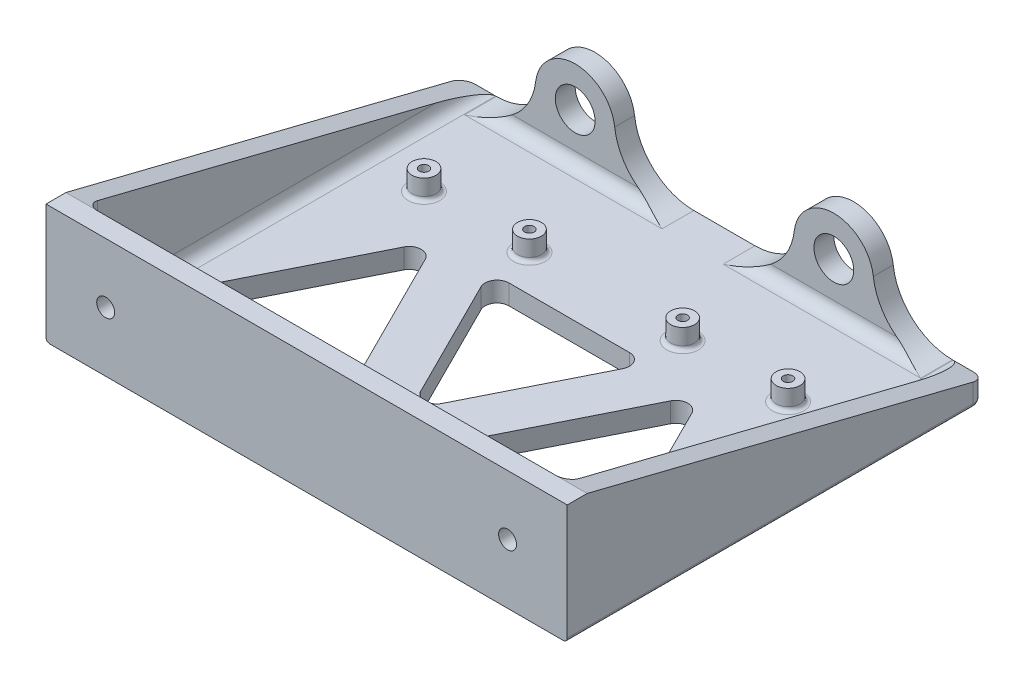
SolidWorks part; units mm, degrees
material "PMMA"
ref_plane "Front Plane" through (0, 0, 0) normal (0, 0, 1) x (1, 0, 0)
ref_plane "Top Plane" through (0, 0, 0) normal (0, 1, 0) x (1, 0, 0)
ref_plane "Right Plane" through (0, 0, 0) normal (1, 0, 0) x (0, 0, -1)
sketch "Sketch1" plane through (0, 0, 0) normal (0, 1, 0) x (1, 0, 0)
  line L7 (-45.75, -29.25) -> (-19.25, -29.25) construction
  line L8 (-45.75, -29.25) -> (-45.75, 29.25) construction
  line L9 (-45.75, 29.25) -> (-19.25, 29.25) construction
  line L10 (-19.25, -29.25) -> (-19.25, 29.25) construction
  line L11 (-45.75, -29.25) -> (-19.25, 29.25) construction
  line L12 (-45.75, 29.25) -> (-19.25, -29.25) construction
  line L13 (19.25, -29.25) -> (45.75, -29.25) construction
  line L14 (19.25, -29.25) -> (19.25, 29.25) construction
  line L15 (19.25, 29.25) -> (45.75, 29.25) construction
  line L16 (45.75, -29.25) -> (45.75, 29.25) construction
  line L17 (19.25, -29.25) -> (45.75, 29.25) construction
  line L18 (19.25, 29.25) -> (45.75, -29.25) construction
  circle A0 centre (-45.75, 29.25) radius 3
  circle A1 centre (-19.25, 29.25) radius 3
  circle A2 centre (-45.75, -29.25) radius 3
  circle A3 centre (-19.25, -29.25) radius 3
  circle A4 centre (19.25, 29.25) radius 3
  circle A5 centre (45.75, 29.25) radius 3
  circle A6 centre (45.75, -29.25) radius 3
  circle A7 centre (-45.75, 29.25) radius 1.2
  circle A8 centre (-19.25, 29.25) radius 1.2
  circle A9 centre (19.25, 29.25) radius 1.2
  circle A10 centre (-45.75, -29.25) radius 1.2
  circle A11 centre (-19.25, -29.25) radius 1.2
  circle A12 centre (45.75, -29.25) radius 1.2
  circle A13 centre (19.25, -29.25) radius 3
  circle A14 centre (19.25, -29.25) radius 1.2
  circle A15 centre (45.75, 29.25) radius 1.2
  point P0 (0, 0)
  point P6 (-32.5, 0)
  point P11 (32.5, 0)
  dimension "D5" = 6
  dimension "D6" = 2.4
  dimension "D1" = 26.5
  dimension "D2" = 58.5
  dimension "D3" = 65
  dimension "D4" = 19.25
extrude "Boss-Extrude1" add sketch "Sketch1" along normal blind 10
sketch "Sketch2" plane through (0, 0, 0) normal (0, 1, 0) x (1, 0, 0)
  line L1 (65.5, 59) -> (-65.5, 59)
  line L2 (65.5, 59) -> (65.5, -41)
  line L3 (65.5, -41) -> (-65.5, -41)
  line L4 (-65.5, 59) -> (-65.5, -41)
  line L5 (65.5, 59) -> (-65.5, -41) construction
  line L6 (65.5, -41) -> (-65.5, 59) construction
  circle A0 centre (45.75, -29.25) radius 1.2
  circle A1 centre (19.25, -29.25) radius 1.2
  circle A2 centre (-19.25, -29.25) radius 1.2
  circle A3 centre (-45.75, -29.25) radius 1.2
  circle A4 centre (-45.75, 29.25) radius 1.2
  circle A5 centre (-19.25, 29.25) radius 1.2
  circle A6 centre (19.25, 29.25) radius 1.2
  circle A7 centre (45.75, 29.25) radius 1.2
  point P0 (0, 9)
  point P33 (0, 9)
  dimension "D3" = 2.4
  dimension "D1" = 100
  dimension "D2" = 65.5
  dimension "D4" = 9
extrude "Boss-Extrude2" add sketch "Sketch2" along normal blind 5
sketch "Sketch5" plane through (0, 0, 41) normal (0, 0, 1) x (1, 0, 0)
  line L0 (65.5, 5) -> (65.5, 0) construction
  line L1 (-65.5, 0) -> (65.5, 0)
  line L2 (-65.5, 0) -> (-65.5, 30)
  line L3 (-65.5, 30) -> (65.5, 30)
  line L4 (65.5, 0) -> (65.5, 30)
  dimension "D1" = 30
extrude "Boss-Extrude4" add sketch "Sketch5" along normal blind 5
sketch "Sketch6" plane through (-65.5, 0, 0) normal (-1, 0, 0) x (0, 0, 1)
  line L0 (-59, 5) -> (41, 30)
  line L1 (41, 30) -> (41, 5)
  line L2 (41, 5) -> (-59, 5)
extrude "Boss-Extrude5" add sketch "Sketch6" against normal blind 5
mirror "Mirror1" about plane through (0, 0, 0) normal (1, 0, 0) of "Boss-Extrude5"
fillet "Fillet2" radius 3 7 edges at (-60.5, 5, -9) (-60.5, 17.5, 41) (0, 5, 41) (60.5, 17.5, 41) (60.5, 5, -9) (65.5, 2.5, -59) (-65.5, 2.5, -59)
sketch "Sketch7" plane through (0, 0, 46) normal (0, 0, 1) x (1, 0, 0)
  line L0 (-65.5, 30) -> (-65.5, 0) construction
  line L1 (65.5, 0) -> (65.5, 30) construction
  circle A0 centre (-50.5, 15) radius 2.25
  circle A1 centre (50.5, 15) radius 2.25
  point P8 (-65.5, 15)
  dimension "D1" = 4.5
  dimension "D2" = 15
  dimension "D3" = 15
extrude "Cut-Extrude2" cut sketch "Sketch7" against normal blind 5
sketch "Sketch8" plane through (0, 0, -59) normal (0, 0, -1) x (-1, 0, 0)
  line L1 (-57.5, 5) -> (57.5, 5) construction
  line L2 (-42.5, 17) -> (-42.5, 0)
  line L3 (-62.5, 0) -> (62.5, 0) construction
  line L4 (-42.5, 0) -> (-22.5, 0)
  line L5 (-22.5, 0) -> (-22.5, 17)
  circle A0 centre (-32.5, 17) radius 5
  arc A2 (-42.5, 17) -> (-22.5, 17) centre (-32.5, 17) cw
  dimension "D1" = 10
  dimension "D2" = 12
  dimension "D4" = 10
  dimension "D3" = 32.5
extrude "Boss-Extrude6" add sketch "Sketch8" against normal blind 5
fillet "Fillet5" radius 15 2 edges at (22.5, 5, -56.5) (42.5, 5, -56.5)
fillet "Fillet6" radius 3 1 edges at (32.5, 5, -54)
mirror "Mirror2" about plane through (0, 0, 0) normal (1, 0, 0) of "Fillet5", "Fillet6", "Boss-Extrude6"
fillet "Fillet7" radius 1 8 edges at (-19.25, 5, -32.25) (-45.75, 5, -32.25) (-45.75, 5, 26.25) (-19.25, 5, 26.25) (45.75, 5, -32.25) (19.25, 5, -32.25) (19.25, 5, 26.25) (45.75, 5, 26.25)
fillet "Fillet8" radius 1 5 edges at (65.5, 0, -5) (64.6213, 0, -58.1213) (-65.5, 0, -5) (-64.6213, 0, -58.1213) (0, 0, -59)
sketch "Sketch11" plane through (0, 5, 0) normal (0, 1, 0) x (1, 0, 0)
  line L0 (-1035.1256, 20) -> (48964.8744, 20) construction
  line L9 (-1034.0764, -20) -> (48965.9236, -20) construction
  line L10 (-53.5, -20) -> (-33.5, 20)
  line L11 (-33.5, 20) -> (-13.5, -20)
  line L12 (-53.5, -20) -> (-13.5, -20)
  line L13 (-20, 20) -> (0, -20)
  line L14 (0, -20) -> (20, 20)
  line L15 (20, 20) -> (-20, 20)
  line L16 (33.5, 20) -> (13.5, -20)
  line L17 (13.5, -20) -> (53.5, -20)
  line L18 (53.5, -20) -> (33.5, 20)
  line L19 (-65.5, -41) -> (-65.5, 56) construction
  line L20 (65.5, -41) -> (65.5, 56) construction
  dimension "D1" = 40
  dimension "D2" = 12
  dimension "D3" = 12
  dimension "D4" = 20
  dimension "D5" = 40
extrude "Cut-Extrude3" cut sketch "Sketch11" against normal blind 5
fillet "Fillet9" radius 3 9 edges at (53.5, 2.5, 20) (13.5, 2.5, 20) (0, 2.5, 20) (-13.5, 2.5, 20) (-53.5, 2.5, 20) (33.5, 2.5, -20) (20, 2.5, -20) (-20, 2.5, -20) (-33.5, 2.5, -20)
